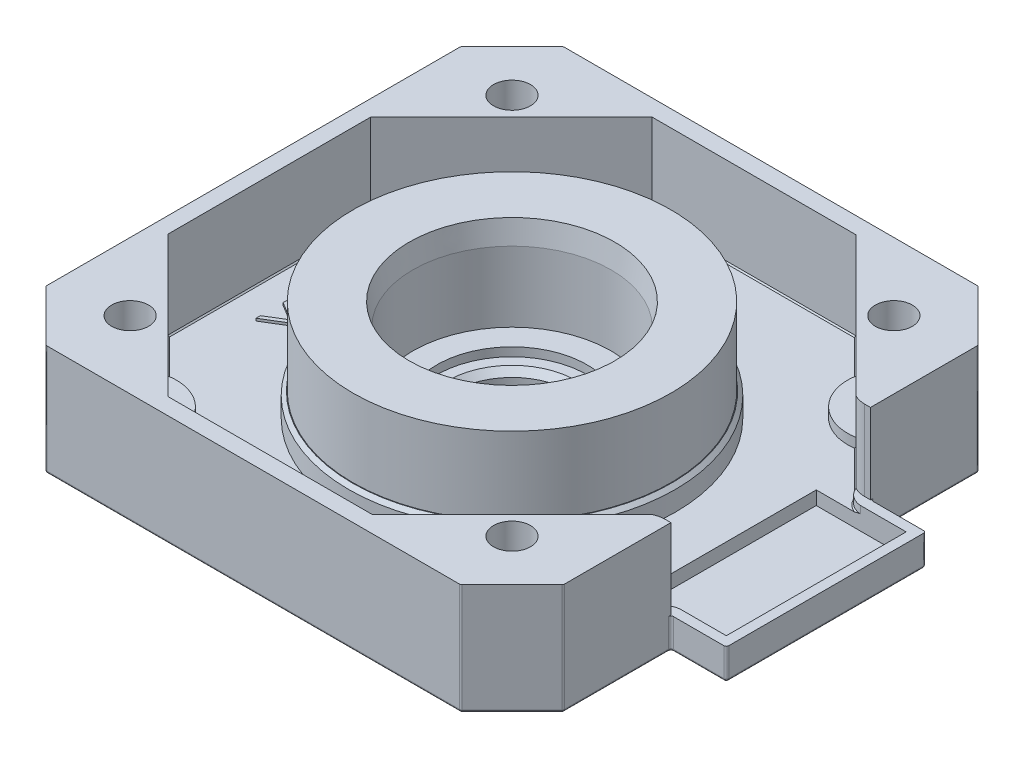
SolidWorks part; units mm, degrees
material "Liga 6061"
ref_plane "Plano frontal" through (0, 0, 0) normal (0, 0, 1) x (1, 0, 0)
ref_plane "Plano superior" through (0, 0, 0) normal (0, 1, 0) x (1, 0, 0)
ref_plane "Plano direito" through (0, 0, 0) normal (1, 0, 0) x (0, 0, -1)
sketch "Esboço1" plane through (0, 0, 0) normal (0, 1, 0) x (1, 0, 0)
  line L0 (18.9151, -18.9151) -> (-18.9151, 18.9151)
  line L1 (-16.83, -21) -> (16.83, -21)
  line L2 (-21, -16.83) -> (-21, 16.83)
  line L3 (-16.83, 21) -> (16.83, 21)
  line L4 (21, -16.83) -> (21, 16.83)
  line L5 (-21, -21) -> (21, 21) construction
  line L6 (-21, 21) -> (21, -21) construction
  line L7 (-18.9151, -18.9151) -> (18.9151, 18.9151)
  line L8 (-21, 16.83) -> (-16.83, 21)
  line L9 (16.83, 21) -> (21, 16.83)
  line L10 (-21, -16.83) -> (-16.83, -21)
  line L11 (16.83, -21) -> (21, -16.83)
  point P0 (0, 0)
  point P9 (0, 0)
  point P12 (0, 0)
  dimension "D1" = 42
  dimension "D2" = 42
  dimension "D3" = 53.5
  dimension "D4" = 53.5
extrude "Ressalto-extrusão1" add sketch "Esboço1" along normal mid plane 9 contours L10 L1 L11 L4 L9 L3 L8 L2
sketch "Esboço2" plane through (0, -4.5, 0) normal (0, -1, 0) x (1, 0, 0)
  line L0 (21, 16.83) -> (21, -16.83) construction
  line L1 (21, 16.83) -> (21, -16.83)
  line L2 (0, 0) -> (0, 8.9811) construction
  line L3 (21, -8.1) -> (25.5, -8.1)
  line L4 (21, -8.1) -> (21, 8.1)
  line L5 (21, 8.1) -> (25.5, 8.1)
  line L6 (25.5, -8.1) -> (25.5, 8.1)
  line L7 (0, 0) -> (51, 0) construction
  point P6 (21, 0)
  point P7 (25.5, 0)
  dimension "D1" = 16.2
  dimension "D2" = 4.5
extrude "Ressalto-extrusão2" add sketch "Esboço2" against normal blind 2.5 separate body contours L3 L6 L5 L1
combine bodies "Combinar1" operation type add bodies to combine 101 102
sketch "Esboço3" plane through (0, 4.5, 0) normal (0, 1, 0) x (1, 0, 0)
  line L0 (0, 0) -> (0, 11.4607) construction
  line L1 (0, 0) -> (11.5472, 0) construction
  circle A0 centre (-15.5, 15.5) radius 1.5
  circle A1 centre (15.5, 15.5) radius 1.5
  circle A2 centre (-15.5, -15.5) radius 1.5
  circle A3 centre (15.5, -15.5) radius 1.5
  dimension "D5" = 3
  dimension "D6" = 31
  dimension "D7" = 31
  dimension "D1" = 31
  dimension "D2" = 31
  dimension "D3" = 31
  dimension "D4" = 31
extrude "Corte-extrusão1" cut sketch "Esboço3" against normal through all
sketch "Esboço4" plane through (0, -4.5, 0) normal (0, -1, 0) x (1, 0, 0)
  circle A0 centre (-15.5, 15.5) radius 3.25
  circle A1 centre (15.5, 15.5) radius 3.25
  circle A2 centre (15.5, -15.5) radius 3.25
  circle A3 centre (-15.5, -15.5) radius 3.25
  dimension "D1" = 6.5
extrude "Corte-extrusão2" cut sketch "Esboço4" against normal blind 2.5
sketch "Esboço5" plane through (0, 4.5, 0) normal (0, 1, 0) x (1, 0, 0)
  line L0 (0, 0) -> (0, 39.3) construction
  line L1 (0, 0) -> (39.2, 0) construction
  line L2 (-19.7, 8.2305) -> (-8.2805, 19.65)
  line L3 (-8.2805, 19.65) -> (8.2805, 19.65)
  line L4 (8.2805, 19.65) -> (19.6, 8.3305)
  line L5 (19.6, 8.3305) -> (19.6, 8.1)
  line L6 (19.6, -8.3305) -> (8.2805, -19.65)
  line L7 (8.2805, -19.65) -> (-8.2805, -19.65)
  line L8 (-8.2805, -19.65) -> (-19.7, -8.2305)
  line L9 (-19.7, -8.2305) -> (-19.7, 8.2305)
  line L10 (-21, -16.83) -> (-21, 16.83) construction
  line L11 (-21, 16.83) -> (-16.83, 21) construction
  line L12 (16.83, -21) -> (21, -16.83) construction
  line L13 (-21, -16.83) -> (-16.83, -21) construction
  line L14 (25.5, 8.1) -> (25.5, -8.1)
  line L15 (19.6, -8.1) -> (19.6, -8.3305)
  line L17 (21, 8.1) -> (25.5, 8.1) construction
  line L18 (21, -8.1) -> (25.5, -8.1) construction
  line L19 (21, 8.1) -> (25.5, 8.1)
  line L20 (21, -8.1) -> (25.5, -8.1)
  line L21 (21, 8.1) -> (19.6, 8.1)
  line L22 (21, -8.1) -> (19.6, -8.1)
  point P16 (0, 19.65)
  point P18 (0, -19.65)
  dimension "D4" = 7
  dimension "D5" = 7
  dimension "D1" = 39.3
  dimension "D2" = 1.3
  dimension "D3" = 39.3
  dimension "D6" = 39.3
extrude "Corte-extrusão3" cut sketch "Esboço5" against normal blind 6.4
fillet "Filete2" radius 2 2 edges at (19.6, 1.3, -8.1) (19.6, 1.3, 8.1)
sketch "Esboço7" plane through (0, -1.9, 0) normal (0, 1, 0) x (1, 0, 0)
  line L0 (-19.7, 8.2305) -> (-19.7, -8.2305) construction
  line L1 (-19.7, -8.2305) -> (-8.2805, -19.65) construction
  line L2 (-8.2805, -19.65) -> (8.2805, -19.65) construction
  line L3 (8.2805, -19.65) -> (19.6, -8.3305) construction
  line L4 (20.5321, -8.1) -> (21, -8.1) construction
  line L5 (21, 8.1) -> (21, -8.1) construction
  line L6 (21, 8.1) -> (20.5321, 8.1) construction
  line L7 (19.6, 8.3305) -> (8.2805, 19.65) construction
  line L8 (8.2805, 19.65) -> (-8.2805, 19.65) construction
  line L9 (-8.2805, 19.65) -> (-19.7, 8.2305) construction
  line L10 (-19.7, 8.2305) -> (-19.7, -8.2305)
  line L11 (-19.7, -8.2305) -> (-16.1276, -11.8029)
  line L12 (-8.2805, -19.65) -> (8.2805, -19.65)
  line L13 (8.2805, -19.65) -> (11.8029, -16.1276)
  line L14 (20.5321, -8.1) -> (21, -8.1)
  line L15 (21, 8.1) -> (21, -8.1)
  line L16 (21, 8.1) -> (20.5321, 8.1)
  line L17 (19.6, 8.3305) -> (16.1276, 11.8029)
  line L18 (8.2805, 19.65) -> (-8.2805, 19.65)
  line L19 (-8.2805, 19.65) -> (-11.8029, 16.1276)
  line L20 (11.8029, 16.1276) -> (8.2805, 19.65)
  line L21 (16.1276, -11.8029) -> (19.6, -8.3305)
  line L22 (-11.8029, -16.1276) -> (-8.2805, -19.65)
  line L23 (-16.1276, 11.8029) -> (-19.7, 8.2305)
  arc A0 (-16.1276, 11.8029) -> (-11.8029, 16.1276) centre (-15.5, 15.5) ccw
  arc A1 (11.8029, 16.1276) -> (16.1276, 11.8029) centre (15.5, 15.5) ccw
  arc A2 (16.1276, -11.8029) -> (11.8029, -16.1276) centre (15.5, -15.5) ccw
  arc A3 (-11.8029, -16.1276) -> (-16.1276, -11.8029) centre (-15.5, -15.5) ccw
  arc A4 (20.5321, -8.1) -> (19.6, -8.3305) centre (20.5321, -10.1) ccw construction
  arc A5 (19.6, 8.3305) -> (20.5321, 8.1) centre (20.5321, 10.1) ccw construction
  arc A6 (20.5321, -8.1) -> (19.6, -8.3305) centre (20.5321, -10.1) ccw
  arc A7 (19.6, 8.3305) -> (20.5321, 8.1) centre (20.5321, 10.1) ccw
  dimension "D1" = 7.5
extrude "Corte-extrusão13" cut sketch "Esboço7" against normal blind 0.1
sketch "Esboço8" plane through (0, -2, 0) normal (0, 1, 0) x (1, 0, 0)
  line L16 (25.5, 8.1) -> (21, 8.1)
  line L17 (21, 8.1) -> (20.5321, 8.1)
  line L18 (19.6, 8.3305) -> (16.1276, 11.8029)
  line L19 (11.8029, 16.1276) -> (8.2805, 19.65)
  line L20 (8.2805, 19.65) -> (-8.2805, 19.65)
  line L21 (-8.2805, 19.65) -> (-11.8029, 16.1276)
  line L22 (-16.1276, 11.8029) -> (-19.7, 8.2305)
  line L23 (-19.7, 8.2305) -> (-19.7, -8.2305)
  line L24 (-19.7, -8.2305) -> (-16.1276, -11.8029)
  line L25 (-11.8029, -16.1276) -> (-8.2805, -19.65)
  line L26 (-8.2805, -19.65) -> (8.2805, -19.65)
  line L27 (8.2805, -19.65) -> (11.8029, -16.1276)
  line L28 (16.1276, -11.8029) -> (19.6, -8.3305)
  line L29 (20.5321, -8.1) -> (21, -8.1)
  line L30 (21, -8.1) -> (25.5, -8.1)
  line L31 (25.5, -8.1) -> (25.5, 8.1)
  line L32 (25.5, 8.1) -> (21, 8.1)
  line L33 (21, 8.1) -> (20.5321, 8.1)
  line L34 (19.6, 8.3305) -> (16.1276, 11.8029)
  line L35 (11.8029, 16.1276) -> (8.2805, 19.65)
  line L36 (8.2805, 19.65) -> (-8.2805, 19.65)
  line L37 (-8.2805, 19.65) -> (-11.8029, 16.1276)
  line L38 (-16.1276, 11.8029) -> (-19.7, 8.2305)
  line L39 (-19.7, 8.2305) -> (-19.7, -8.2305)
  line L40 (-19.7, -8.2305) -> (-16.1276, -11.8029)
  line L41 (-11.8029, -16.1276) -> (-8.2805, -19.65)
  line L42 (-8.2805, -19.65) -> (8.2805, -19.65)
  line L43 (8.2805, -19.65) -> (11.8029, -16.1276)
  line L44 (16.1276, -11.8029) -> (19.6, -8.3305)
  line L45 (20.5321, -8.1) -> (21, -8.1)
  line L46 (21, -8.1) -> (25.5, -8.1)
  line L47 (25.5, -8.1) -> (25.5, 8.1)
  arc A6 (19.6, 8.3305) -> (20.5321, 8.1) centre (20.5321, 10.1) ccw
  arc A7 (11.8029, 16.1276) -> (16.1276, 11.8029) centre (15.5, 15.5) ccw
  arc A8 (-16.1276, 11.8029) -> (-11.8029, 16.1276) centre (-15.5, 15.5) ccw
  arc A9 (-11.8029, -16.1276) -> (-16.1276, -11.8029) centre (-15.5, -15.5) ccw
  arc A10 (16.1276, -11.8029) -> (11.8029, -16.1276) centre (15.5, -15.5) ccw
  arc A11 (20.5321, -8.1) -> (19.6, -8.3305) centre (20.5321, -10.1) ccw
  arc A12 (19.6, 8.3305) -> (20.5321, 8.1) centre (20.5321, 10.1) ccw
  arc A13 (11.8029, 16.1276) -> (16.1276, 11.8029) centre (15.5, 15.5) ccw
  arc A14 (-16.1276, 11.8029) -> (-11.8029, 16.1276) centre (-15.5, 15.5) ccw
  arc A15 (-11.8029, -16.1276) -> (-16.1276, -11.8029) centre (-15.5, -15.5) ccw
  arc A16 (16.1276, -11.8029) -> (11.8029, -16.1276) centre (15.5, -15.5) ccw
  arc A17 (20.5321, -8.1) -> (19.6, -8.3305) centre (20.5321, -10.1) ccw
  dimension "D1" = 0
extrude "Corte-extrusão14" cut sketch "Esboço8" against normal blind 0.7
sketch "Esboço9" plane through (0, -2.7, 0) normal (0, 1, 0) x (1, 0, 0)
  line L0 (20.5321, 8.1) -> (21, 8.1) construction
  line L10 (25.5, 8.1) -> (21, 8.1) construction
  line L11 (25.5, 8.1) -> (21, 8.1)
  line L15 (21, 7.3) -> (20.5321, 7.3)
  line L16 (20.5321, -7.3) -> (21, -7.3)
  line L17 (21, -7.3) -> (24.7, -7.3)
  line L18 (24.7, -7.3) -> (24.7, 7.3)
  line L19 (24.7, 7.3) -> (21, 7.3)
  line L20 (20.5321, 8.1) -> (21, 8.1)
  line L22 (21, -7.3) -> (24.7, -7.3)
  line L23 (24.7, -7.3) -> (24.7, 7.3)
  line L24 (24.7, 7.3) -> (21, 7.3)
  line L26 (25.5, -8.1) -> (25.5, 8.1) construction
  line L27 (25.5, -8.1) -> (25.5, 8.1)
  line L28 (21, -8.1) -> (25.5, -8.1) construction
  line L29 (21, -8.1) -> (25.5, -8.1)
  line L30 (20.5321, -8.1) -> (21, -8.1) construction
  line L31 (20.5321, -8.1) -> (21, -8.1)
  arc A2 (19.6, 8.3305) -> (20.5321, 8.1) centre (20.5321, 10.1) ccw construction
  arc A3 (19.6, 8.3305) -> (20.5321, 8.1) centre (20.5321, 10.1) ccw
  arc A4 (20.5321, -8.1) -> (19.6, -8.3305) centre (20.5321, -10.1) ccw construction
  arc A5 (20.5321, -8.1) -> (19.6, -8.3305) centre (20.5321, -10.1) ccw
  arc A6 (21, -7.3) -> (19.6, -8.3305) centre (21.0963, -8.8971) ccw
  arc A7 (19.6, 8.3305) -> (21, 7.3) centre (21.0963, 8.8971) ccw
  dimension "D2" = 1.6
  dimension "D3" = 1.6
  dimension "D1" = 0.8
extrude "Ressalto-extrusão3" add sketch "Esboço9" along normal blind 0.7
sketch "Esboço10" plane through (0, -2.7, 0) normal (0, 1, 0) x (1, 0, 0)
  line L0 (21, 7.3) -> (24.7, 7.3) construction
  line L1 (21, 7.3) -> (24.7, 7.3)
  line L2 (24.7, 7.3) -> (24.7, -7.3) construction
  line L3 (24.7, 7.3) -> (24.7, -7.3)
  line L4 (24.7, -7.3) -> (21, -7.3) construction
  line L5 (24.7, -7.3) -> (21, -7.3)
  line L6 (17.4, 7.3) -> (21, 7.3)
  line L7 (17.4, -7.3) -> (21, -7.3)
  line L9 (17.4, -7.3) -> (17.4, 7.3)
  point P12 (17.4, 0)
  dimension "D1" = 7.3
extrude "Corte-extrusão15" cut sketch "Esboço10" against normal blind 1.1
sketch "Esboço11" plane through (0, -2.7, 0) normal (0, 1, 0) x (1, 0, 0)
  circle A0 centre (0, 0) radius 4.75
  dimension "D1" = 9.5
extrude "Corte-extrusão16" cut sketch "Esboço11" against normal through all
chamfer "Chanfro1" distance 0.5 angle 45 1 edges at (0, -2.7, 4.75)
fillet "Filete3" radius 0.5 1 edges at (0, -4.5, 4.75)
fillet "Filete4" radius 0.2 28 edges at (21, 0, -16.83) (16.83, 0, -21) (-21, 0, 16.83) (-16.83, 0, 21) (-16.83, 0, -21) (-21, 0, -16.83) (16.83, 0, 21) (21, -3.25, 8.1) (21, -3.25, -8.1) (21, 0, 16.83) (25.5, -3.25, -8.1) (25.5, -3.25, 8.1) (25.5, -4.5, 0) (23.25, -4.5, -8.1) (23.25, -4.5, 8.1) (21, -4.5, 12.465) (18.915, -4.5, 18.915) (0, -4.5, 21) (-18.915, -4.5, 18.915) (-21, -4.5, 0) (-18.915, -4.5, -18.915) (18.915, -4.5, -18.915) (21, -4.5, -12.465) (-15.5, -4.5, 12.25) (15.5, -4.5, 12.25) (-15.5, -4.5, -18.75) (15.5, -4.5, -18.75) (0, -4.5, -21)
chamfer "Chanfro2" distance 0.1 angle 45 13 edges at (20.1478, -2.7, -7.6085) (17.8638, -2.7, -10.0667) (10.0417, -2.7, -17.8888) (0, -2.7, -19.65) (-10.0417, -2.7, -17.8888) (-17.9138, -2.7, -10.0167) (-19.7, -2.7, 0) (-17.9138, -2.7, 10.0167) (-10.0417, -2.7, 17.8888) (0, -2.7, 19.65) (10.0417, -2.7, 17.8888) (17.8638, -2.7, 10.0667) (20.1478, -2.7, 7.6085)
sketch "Esboço12" plane through (0, -2.7, 0) normal (0, 1, 0) x (1, 0, 0)
  circle A0 centre (0, 0) radius 13.25
  circle A1 centre (0, 0) radius 8.05
  dimension "D1" = 26.5
  dimension "D2" = 16.1
extrude "Ressalto-extrusão4" add sketch "Esboço12" along normal blind 8.2
sketch "Esboço13" plane through (0, 5.5, 0) normal (0, 1, 0) x (1, 0, 0)
  circle A0 centre (0, 0) radius 12.9
  circle A1 centre (0, 0) radius 13.25 construction
  circle A2 centre (0, 0) radius 13.25
  dimension "D1" = 25.8
extrude "Corte-extrusão17" cut sketch "Esboço13" against normal blind 6.3
chamfer "Chanfro3" distance 0.3 angle 45 1 edges at (0, -0.8, 13.25)
sketch "Esboço14" plane through (0, -2.7, 0) normal (0, 1, 0) x (1, 0, 0)
  circle A0 centre (0, 0) radius 6.1
  circle A1 centre (0, 0) radius 8.05 construction
  circle A2 centre (0, 0) radius 8.05
  dimension "D1" = 12.2
extrude "Ressalto-extrusão5" add sketch "Esboço14" along normal blind 0.7
chamfer "Chanfro4" distance 0.3 distance2 1.8 1 edges at (0, 5.5, 8.05)
sketch "Esboço15" plane through (0, -2.7, 0) normal (0, 1, 0) x (1, 0, 0)
  line L0 (-3.1575, -14.9106) -> (3.1575, -14.9106) construction
  line L1 (-13.7103, -7.4418) -> (-13.7103, 7.3494) construction
  text T0 "5" font "Century Gothic" height in points 10
  text T1 "YW"
  point P2 (0, -14.9106)
extrude "Ressalto-extrusão6" add sketch "Esboço15" along normal blind 0.2
